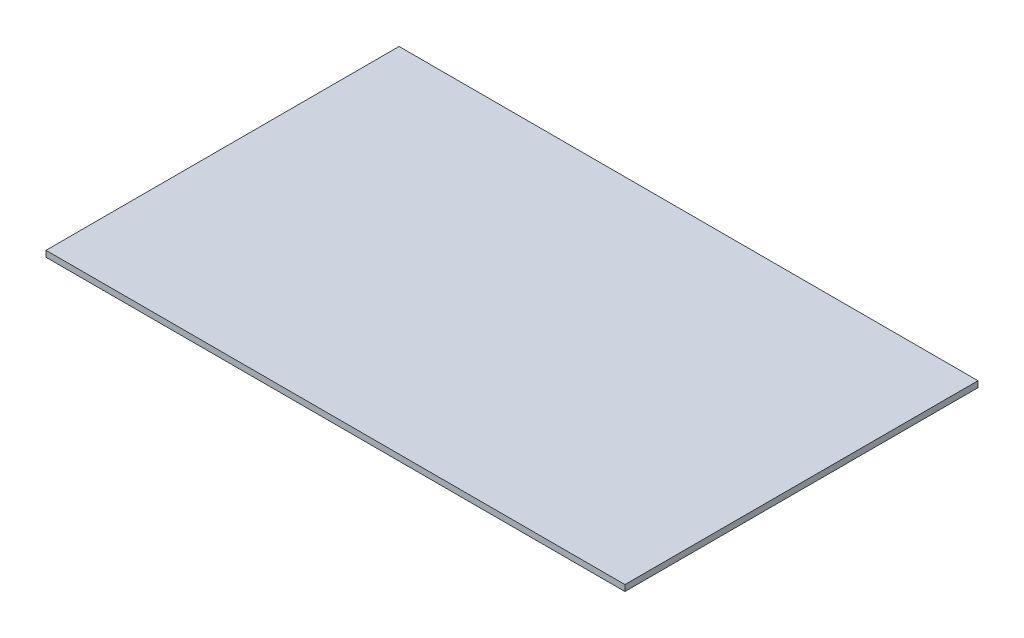
SolidWorks part; units mm, degrees
material "5052-H34"
ref_plane "Front Plane" through (0, 0, 0) normal (0, 0, 1) x (1, 0, 0)
ref_plane "Top Plane" through (0, 0, 0) normal (0, 1, 0) x (1, 0, 0)
ref_plane "Right Plane" through (0, 0, 0) normal (1, 0, 0) x (0, 0, -1)
sketch "Sketch2" plane through (0, 0, 0) normal (0, 0, 1) x (1, 0, 0)
  line L0 (0, 0) -> (455, 0)
  line L1 (0, 0) -> (0, 4.7625)
  line L2 (0, 4.7625) -> (455, 4.7625)
  line L3 (455, 4.7625) -> (455, 0)
extrude "Boss-Extrude1" add sketch "Sketch2" along normal blind 277.48 contours L2 L3 L0 L1
